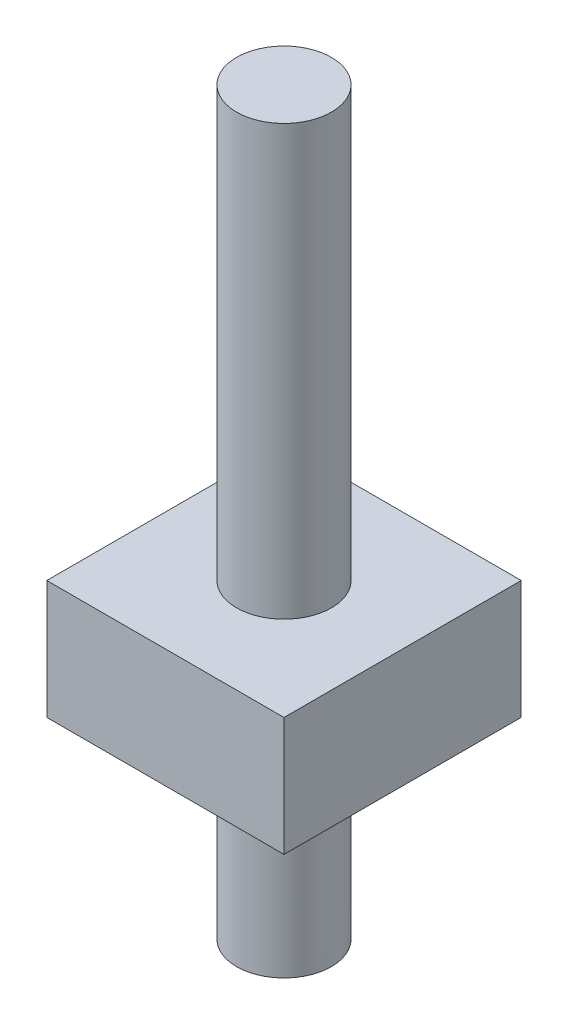
SolidWorks part; units mm, degrees
ref_plane "Front Plane" through (0, 0, 0) normal (0, 0, 1) x (1, 0, 0)
ref_plane "Top Plane" through (0, 0, 0) normal (0, 1, 0) x (1, 0, 0)
ref_plane "Right Plane" through (0, 0, 0) normal (1, 0, 0) x (0, 0, -1)
sketch "Sketch1" plane through (0, 0, 0) normal (0, 1, 0) x (1, 0, 0)
  circle A0 centre (0, 0) radius 2
  dimension "D1" = 4
extrude "Boss-Extrude1" add sketch "Sketch1" along normal blind 15.6 and the other way blind 15.6
sketch "Sketch3" plane through (0, 0, 0) normal (1, 0, 0) x (0, 0, -1)
  line L0 (0, 0) -> (0, -5) construction
  line L2 (-5, -2.5) -> (5, -2.5)
  line L3 (-5, -2.5) -> (-5, -7.5)
  line L4 (-5, -7.5) -> (5, -7.5)
  line L5 (5, -2.5) -> (5, -7.5)
  line L6 (-5, -2.5) -> (5, -7.5) construction
  line L7 (-5, -7.5) -> (5, -2.5) construction
  dimension "D1" = 2.5
  dimension "D2" = 5
  dimension "D3" = 10
extrude "Boss-Extrude2" add sketch "Sketch3" along normal blind 5 and the other way blind 5
